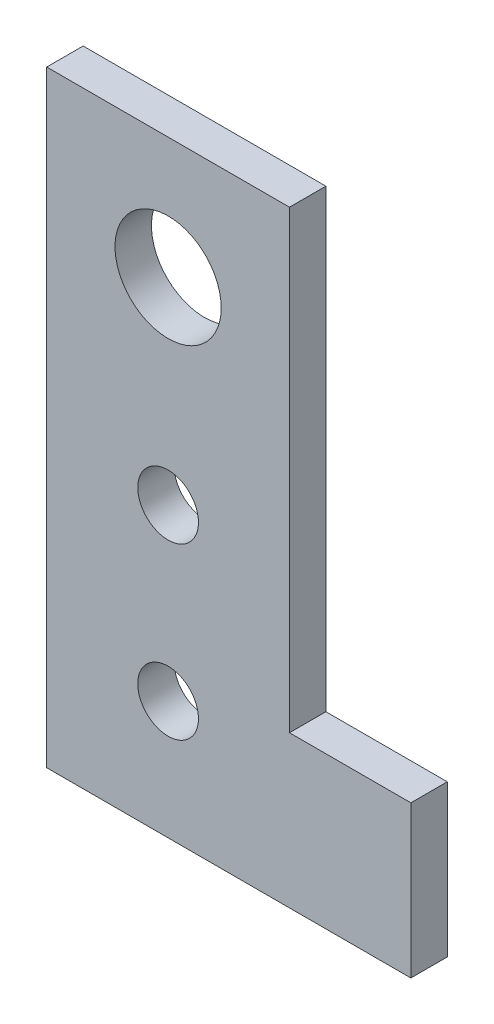
SolidWorks part; units mm, degrees
ref_plane "Спереди" through (0, 0, 0) normal (0, 0, 1) x (1, 0, 0)
ref_plane "Сверху" through (0, 0, 0) normal (0, 1, 0) x (1, 0, 0)
ref_plane "Справа" through (0, 0, 0) normal (1, 0, 0) x (0, 0, -1)
sketch "Эскиз1" plane through (0, 0, 0) normal (0, 0, 1) x (1, 0, 0)
  line L0 (4, 20) -> (4, 0) construction
  line L1 (0, 0) -> (12, 0)
  line L2 (0, 0) -> (0, 20)
  line L3 (0, 20) -> (8, 20)
  line L4 (8, 5) -> (8, 20)
  line L7 (8, 5) -> (12, 5)
  line L8 (12, 0) -> (12, 5)
  circle A0 centre (4, 16) radius 1.75
  circle A1 centre (4, 9.5) radius 1
  circle A2 centre (4, 3.9) radius 1
  dimension "D3" = 3.5
  dimension "D4" = 6.5
  dimension "D5" = 5.6
  dimension "D6" = 2
  dimension "D7" = 2
  dimension "D8" = 16
  dimension "D1" = 8
  dimension "D2" = 4
  dimension "D9" = 5
  dimension "D10" = 12
base flange "Базовая кромка1" sketch "Эскиз1" thickness 1.2 reverse thickness direction no parameters "D1"=0.7366
sketch "Сгиб-Линии1" plane through (0, 0, 0) normal (0, 1, 0) x (1, 0, 0)
sketch "Граничная рамка1" plane through (0, 0, 0) normal (0, 1, 0) x (1, 0, 0)
sheet metal parameters "Листовой металл3" thickness 1.2 parameters "D1"=0.7366
flat pattern "Развертка3" [suppressed]
sketch "Сгиб-Линии2" plane through (0, 0, 0) normal (0, 1, 0) x (1, 0, 0)
sketch "Граничная рамка2" [suppressed] plane through (0, 0, 0) normal (0, 1, 0) x (1, 0, 0)
